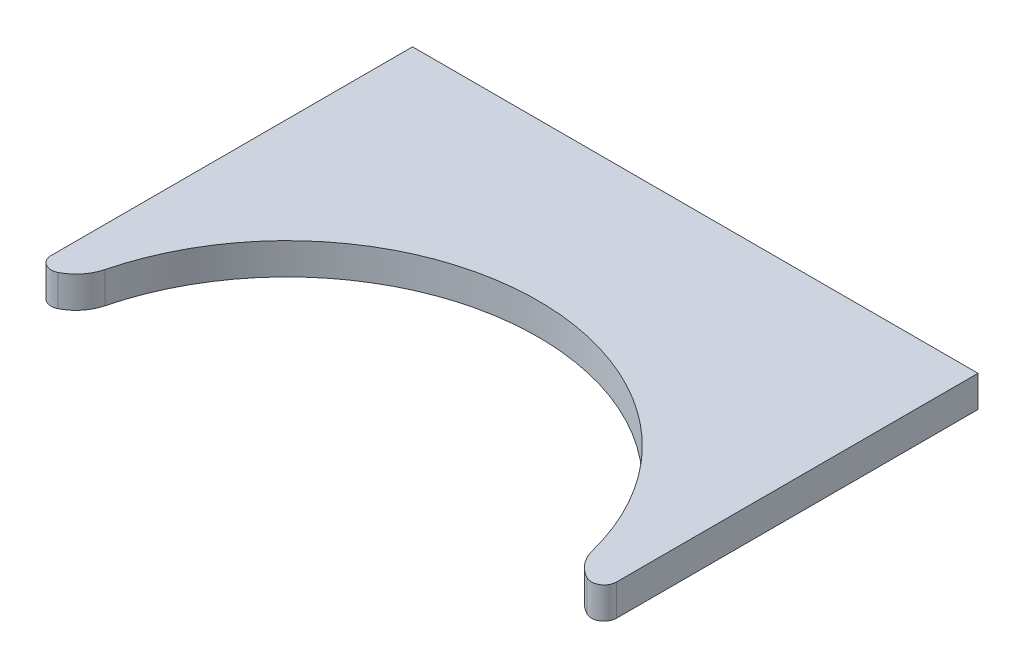
SolidWorks part; units mm, degrees
ref_plane "Front Plane" through (0, 0, 0) normal (0, 0, 1) x (1, 0, 0)
ref_plane "Top Plane" through (0, 0, 0) normal (0, 1, 0) x (1, 0, 0)
ref_plane "Right Plane" through (0, 0, 0) normal (1, 0, 0) x (0, 0, -1)
sketch "Sketch1" plane through (0, 0, 0) normal (0, 1, 0) x (1, 0, 0)
  line L1 (-28.575, 19.05) -> (28.575, 19.05)
  line L2 (-28.575, 19.05) -> (-28.575, -19.05)
  line L3 (-28.575, -19.05) -> (28.575, -19.05)
  line L4 (28.575, 19.05) -> (28.575, -19.05)
  line L5 (-28.575, 19.05) -> (28.575, -19.05) construction
  line L6 (-28.575, -19.05) -> (28.575, 19.05) construction
  point P0 (0, 0)
  dimension "D1" = 57.15
  dimension "D2" = 38.1
extrude "Boss-Extrude1" add sketch "Sketch1" along normal blind 3.175
sketch "Sketch2" plane through (0, 3.175, 0) normal (0, 1, 0) x (1, 0, 0)
  line L2 (-28.575, -19.05) -> (28.575, -19.05) construction
  line L3 (-28.575, -19.05) -> (28.575, -19.05)
  line L5 (28.575, -19.05) -> (28.575, 19.05) construction
  arc A0 (-24.6185, -15.9727) -> (24.6185, -15.9727) centre (0, -22.225) cw
  arc A1 (-28.575, -19.05) -> (-24.6185, -15.9727) centre (-28.575, -14.9679) ccw
  arc A2 (24.6185, -15.9727) -> (28.575, -19.05) centre (28.575, -14.9679) ccw
  point P2 (28.575, -19.05)
  point P3 (0, 0)
  point P4 (0, -20.8359)
  point P5 (0, -20.301)
  point P13 (0, -25.1063)
  point P14 (28.575, -15.4072)
  point P16 (28.2728, -14.5687)
  point P18 (0, -16.5769)
  point P19 (-28.575, -19.05)
  dimension "D1" = 25.4
  dimension "D2" = 3.175
fillet "Fillet1" [suppressed] radius 6.35
fillet "Fillet2" [suppressed] radius 3.175
extrude "Cut-Extrude1" cut sketch "Sketch2" against normal through all
fillet "Fillet3" radius 1.27 2 edges at (28.575, 1.5875, 19.05) (-28.575, 1.5875, 19.05)
